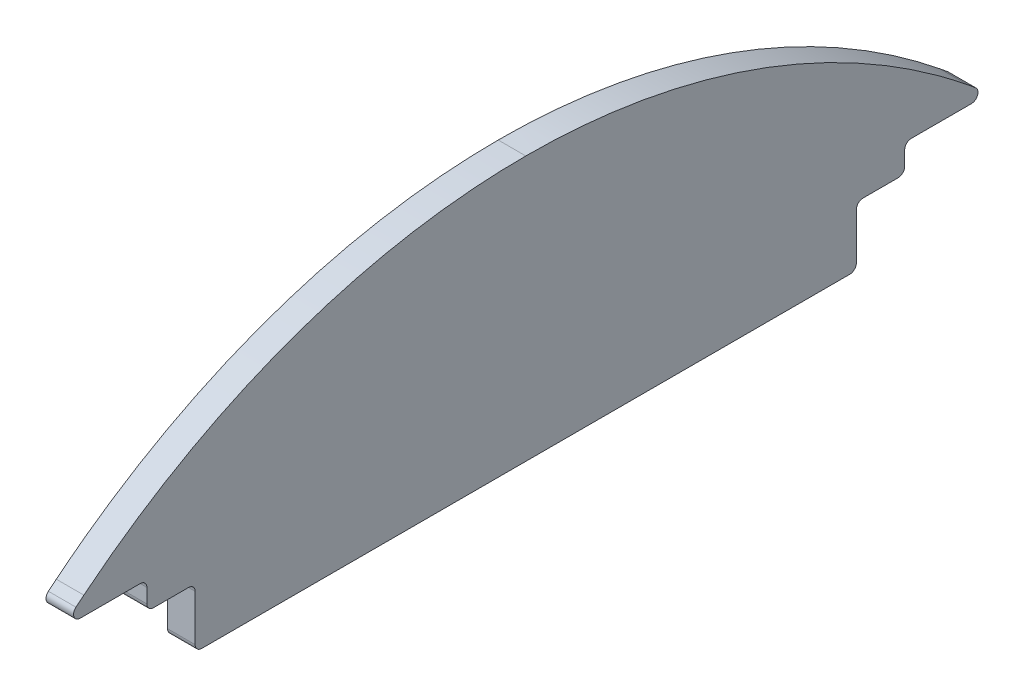
SolidWorks part; units mm, degrees
material "Plywood"
ref_plane "Front Plane" through (0, 0, 0) normal (0, 0, 1) x (1, 0, 0)
ref_plane "Top Plane" through (0, 0, 0) normal (0, 1, 0) x (1, 0, 0)
ref_plane "Right Plane" through (0, 0, 0) normal (1, 0, 0) x (0, 0, -1)
sketch "Sketch1" plane through (0, 0, 0) normal (1, 0, 0) x (0, 0, -1)
  line L0 (-56.8712, -11.8183) -> (56.8712, -11.8183)
  line L1 (-53.4258, -8.6433) -> (-43.6632, -8.6433)
  line L2 (-43.6632, -8.6433) -> (-43.6632, -11.8183)
  line L3 (53.4258, -8.6433) -> (43.6632, -8.6433)
  line L4 (43.6632, -8.6433) -> (43.6632, -11.8183)
  line L5 (-38.1, -11.8183) -> (-38.1, -18.6617)
  line L6 (-38.1, -18.6617) -> (38.1, -18.6617)
  line L7 (38.1, -18.6617) -> (38.1, -11.8183)
  spline S0 degree 3 poles (56.8712, -11.8183) (56.2243, -11.2014) (54.938, -9.9747) (52.9544, -8.2157) (51.5987, -7.0986) (50.9249, -6.5434) knots 0 0 0 0 0.337268 0.670587 1 1 1 1
  spline S1 degree 3 poles (50.9249, -6.5434) (50.1241, -5.9092) (48.5281, -4.6451) (46.0591, -2.8642) (43.5499, -1.1776) (40.9979, 0.4061) (38.4082, 1.8883) (35.7837, 3.2679) (33.1279, 4.5446) (30.4442, 5.7179) (27.7359, 6.7878) (25.0062, 7.7541) (22.2584, 8.6169) (19.4957, 9.3763) (16.7213, 10.0327) (13.9384, 10.5864) (11.15, 11.0378) (8.3592, 11.3881) (5.5692, 11.6354) (2.7828, 11.7897) (0.9265, 11.8088) (0, 11.8183) knots 0 0 0 0 0.055515 0.11065 0.165414 0.219815 0.273862 0.327565 0.380937 0.433988 0.48673 0.539177 0.591342 0.643236 0.694874 0.746267 0.797429 0.848371 0.899107 0.949646 1 1 1 1
  spline S2 degree 3 poles (0, 11.8183) (-0.978, 11.8077) (-2.938, 11.7865) (-5.8796, 11.6145) (-8.8251, 11.3387) (-11.7707, 10.9481) (-14.7129, 10.4447) (-17.6482, 9.8271) (-20.5727, 9.095) (-23.4828, 8.2479) (-26.3747, 7.2856) (-29.2447, 6.2078) (-32.0888, 5.0147) (-34.9032, 3.7065) (-37.6841, 2.2833) (-40.4272, 0.7457) (-43.1291, -0.9052) (-45.784, -2.6708) (-48.3946, -4.5417) (-50.0794, -5.8746) (-50.9249, -6.5434) knots 0 0 0 0 0.053157 0.106521 0.160104 0.213921 0.267985 0.322311 0.376914 0.431808 0.48701 0.542534 0.598395 0.654608 0.711187 0.768144 0.825494 0.883246 0.941412 1 1 1 1
  spline S3 degree 3 poles (-50.9249, -6.5434) (-51.5987, -7.0986) (-52.9544, -8.2157) (-54.938, -9.9747) (-56.2243, -11.2014) (-56.8712, -11.8183) knots 0 0 0 0 0.329413 0.662732 1 1 1 1
  point P15 (0, -18.6617)
  dimension "D1" = 76.2
  dimension "D2" = 3.175
  dimension "D3" = 13.208
  dimension "D4" = 6.8434
extrude "Boss-Extrude1" add sketch "Sketch1" against normal blind 3.175 contours S2 S3 L1 L2 L0 L4 L3 S0 S1 region at (0, -1.9206, -0.0001)
ref_plane "bottom plane reference" through (0, -11.8183, 0) normal (0, -1, 0) x (-1, 0, 0)
extrude "Boss-Extrude2" add sketch "Sketch1<3>" against normal blind 3.175 contours L6 L7 L0 L5 region at (0, -15.24, 0)
sketch "Sketch1<3>" plane through (0, 0, 0) normal (1, 0, 0) x (0, 0, -1) same geometry as "Sketch1"
fillet "Fillet1" radius 0.762 10 edges at (-1.5875, -8.6433, -43.6632) (-1.5875, -11.8183, -43.6632) (-1.5875, -11.8183, 43.6632) (-1.5875, -8.6433, 43.6632) (-1.5875, -18.6617, -38.1) (-1.5875, -11.8183, -38.1) (-1.5875, -18.6617, 38.1) (-1.5875, -11.8183, 38.1)
